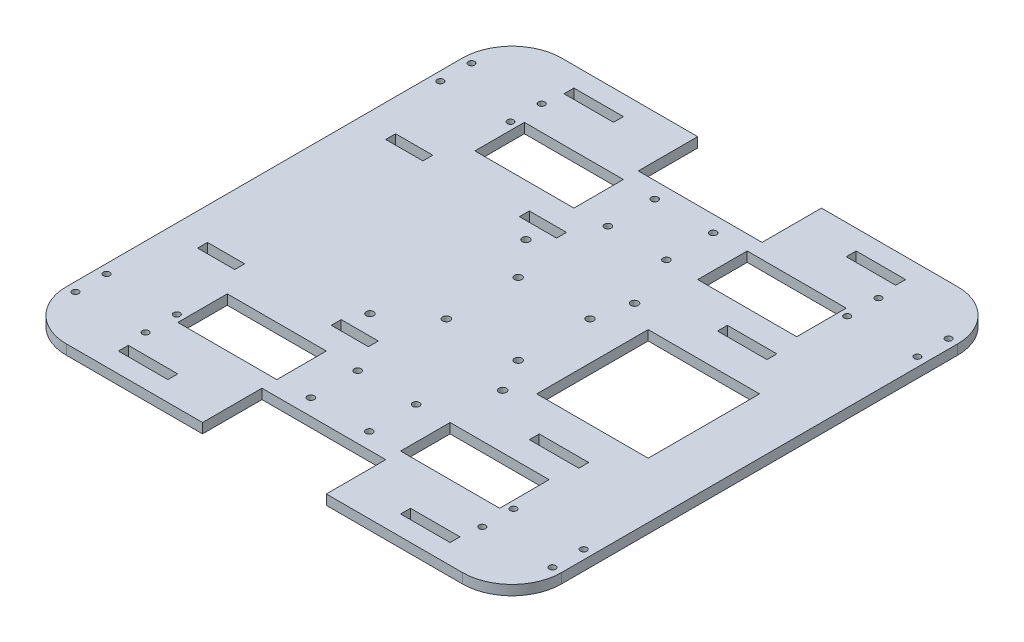
SolidWorks part; units mm, degrees
ref_plane "Front Plane" through (0, 0, 0) normal (0, 0, 1) x (1, 0, 0)
ref_plane "Top Plane" through (0, 0, 0) normal (0, 1, 0) x (1, 0, 0)
ref_plane "Right Plane" through (0, 0, 0) normal (1, 0, 0) x (0, 0, -1)
sketch "Sketch1" plane through (0, 0, 0) normal (0, 1, 0) x (1, 0, 0)
  line L1 (-127, -127) -> (127, -127)
  line L2 (-127, -127) -> (-127, 127)
  line L3 (-127, 127) -> (127, 127)
  line L4 (127, -127) -> (127, 127)
  line L5 (-127, -127) -> (127, 127) construction
  line L6 (-127, 127) -> (127, -127) construction
  point P0 (0, 0)
  dimension "D1" = 254
  dimension "D2" = 254
extrude "Platform-Base" add sketch "Sketch1" along normal blind 5.08
sketch "Sketch9" plane through (0, 5.08, 0) normal (0, 1, 0) x (1, 0, 0)
  line L0 (-127, 0) -> (-85.09, 0) construction
  line L1 (-127, 127) -> (-127, -127) construction
  line L2 (-85.09, 0) -> (-85.09, -116.84) construction
  line L3 (-85.09, 0) -> (-85.09, 116.84) construction
  line L4 (-85.09, 0) -> (85.09, 0) construction
  line L5 (85.09, 0) -> (127, 0) construction
  line L6 (127, -127) -> (127, 127) construction
  line L7 (85.09, 0) -> (85.09, 116.84) construction
  line L8 (85.09, 0) -> (85.09, -116.84) construction
  line L9 (-85.09, -116.84) -> (-127, -116.84) construction
  line L10 (-85.09, -116.84) -> (-85.09, -127) construction
  line L11 (-85.09, -116.84) -> (-59.69, -116.84)
  line L12 (-85.09, -116.84) -> (-85.09, -111.76)
  line L13 (-85.09, -111.76) -> (-59.69, -111.76)
  line L14 (-59.69, -116.84) -> (-59.69, -111.76)
  line L15 (85.09, -116.84) -> (59.69, -116.84)
  line L16 (85.09, -116.84) -> (85.09, -111.76)
  line L17 (85.09, -111.76) -> (59.69, -111.76)
  line L18 (59.69, -116.84) -> (59.69, -111.76)
  line L19 (85.09, 116.84) -> (59.69, 116.84)
  line L20 (85.09, 116.84) -> (85.09, 111.76)
  line L21 (85.09, 111.76) -> (59.69, 111.76)
  line L22 (59.69, 116.84) -> (59.69, 111.76)
  line L23 (-85.09, 116.84) -> (-59.69, 116.84)
  line L24 (-85.09, 116.84) -> (-85.09, 111.76)
  line L25 (-85.09, 111.76) -> (-59.69, 111.76)
  line L26 (-59.69, 116.84) -> (-59.69, 111.76)
  line L27 (-127, -127) -> (127, -127) construction
  line L28 (59.69, 50.8) -> (-22.86, 50.8) construction
  line L29 (59.69, -111.76) -> (59.69, -50.8) construction
  line L34 (59.69, 45.72) -> (59.69, 0) construction
  line L35 (-22.86, 50.8) -> (-41.91, 50.8) construction
  line L36 (-41.91, 50.8) -> (-91.44, 50.8) construction
  line L37 (59.69, -50.8) -> (85.09, -50.8)
  line L38 (59.69, -50.8) -> (59.69, -45.72)
  line L39 (59.69, -45.72) -> (85.09, -45.72)
  line L40 (85.09, -50.8) -> (85.09, -45.72)
  line L41 (59.69, 50.8) -> (85.09, 50.8)
  line L42 (59.69, 50.8) -> (59.69, 45.72)
  line L43 (59.69, 45.72) -> (85.09, 45.72)
  line L44 (85.09, 50.8) -> (85.09, 45.72)
  line L49 (-91.44, 50.8) -> (-110.49, 50.8) construction
  line L50 (-110.49, 50.8) -> (-127, 50.8) construction
  line L51 (-22.86, 45.72) -> (-22.86, -45.72) construction
  line L52 (-22.86, 50.8) -> (-41.91, 50.8)
  line L53 (-22.86, 50.8) -> (-22.86, 45.72)
  line L54 (-22.86, 45.72) -> (-41.91, 45.72)
  line L55 (-41.91, 50.8) -> (-41.91, 45.72)
  line L56 (-91.44, 50.8) -> (-110.49, 50.8)
  line L57 (-91.44, 50.8) -> (-91.44, 45.72)
  line L58 (-91.44, 45.72) -> (-110.49, 45.72)
  line L59 (-110.49, 50.8) -> (-110.49, 45.72)
  line L68 (-41.91, -45.72) -> (-91.4459, -45.72) construction
  line L69 (59.69, -50.8) -> (-22.86, -50.8) construction
  line L70 (-22.86, -45.72) -> (-41.91, -45.72)
  line L71 (59.69, -45.72) -> (59.69, 0) construction
  line L72 (-22.86, -45.72) -> (-22.86, -50.8)
  line L73 (-22.86, -50.8) -> (-41.91, -50.8)
  line L74 (-41.91, -45.72) -> (-41.91, -50.8)
  line L75 (-91.4459, -45.72) -> (-110.4959, -45.72)
  line L76 (-91.4459, -45.72) -> (-91.4459, -50.8)
  line L77 (-91.4459, -50.8) -> (-110.4959, -50.8)
  line L78 (-110.4959, -45.72) -> (-110.4959, -50.8)
  dimension "D1" = 41.91
  dimension "D2" = 5.08
  dimension "D3" = 25.4
  dimension "D4" = 10.16
  dimension "D6" = 16.51
  dimension "D7" = 19.05
  dimension "D8" = 49.53
  dimension "D9" = 19.05
  dimension "D5" = 45.72
extrude "Cut-Extrude6" cut sketch "Sketch9" against normal through all
ref_axis "Axis1" through (-127, 5.08, 0) along (0, -1, 0)
ref_plane "Plane1" through (0, 0, 0) normal (0, 0, 1) x (0, -1, 0)
sketch "Sketch3" plane through (0, 5.08, 0) normal (0, 1, 0) x (1, 0, 0)
  line L0 (127, 0) -> (-126.5787, 0) construction
  line L1 (127, -127) -> (127, 127) construction
  line L2 (-127, -127) -> (127, -127) construction
  line L3 (0, -127) -> (0, 127) construction
  line L4 (127, 127) -> (-127, 127) construction
  line L5 (0.2106, 0) -> (0, -76.2) construction
  line L7 (15, -64.2) -> (-15, -64.2) construction
  line L8 (15, -64.2) -> (15, -88.2) construction
  line L9 (15, -88.2) -> (-15, -88.2) construction
  line L10 (-15, -64.2) -> (-15, -88.2) construction
  line L11 (15, -64.2) -> (-15, -88.2) construction
  line L12 (15, -88.2) -> (-15, -64.2) construction
  circle A0 centre (15, -64.2) radius 1.75
  circle A1 centre (15, -88.2) radius 1.75
  circle A2 centre (-15, -88.2) radius 1.75
  circle A3 centre (-15, -64.2) radius 1.75
  dimension "D1" = 76.2
  dimension "D2" = 24
  dimension "D3" = 30
extrude "Cut-Extrude1" cut sketch "Sketch3" against normal through all
mirror "Mirror2" about plane through (0, 0, 0) normal (0, 0, 1) of "Cut-Extrude1"
sketch "Sketch4" plane through (0, 5.08, 0) normal (0, 1, 0) x (1, 0, 0)
  line L0 (-127, -127) -> (127, -127) construction
  line L1 (0, -127) -> (0, -111.76) construction
  line L3 (31.75, -96.52) -> (-31.75, -96.52)
  line L4 (31.75, -96.52) -> (31.75, -127)
  line L5 (31.75, -127) -> (-31.75, -127)
  line L6 (-31.75, -96.52) -> (-31.75, -127)
  line L7 (31.75, -96.52) -> (-31.75, -127) construction
  line L8 (31.75, -127) -> (-31.75, -96.52) construction
  dimension "D1" = 63.5
  dimension "D2" = 30.48
  dimension "D3" = 15.24
extrude "Cut-Extrude2" cut sketch "Sketch4" against normal through all
mirror "Mirror3" about plane through (0, 0, 0) normal (0, 0, 1) of "Cut-Extrude2"
ref_axis "Axis5" [suppressed] through (0, 7.62, -96.52) along (0, 0, 1)
ref_plane "Plane2" [suppressed] through (0, 0, 0) normal (-1, 0, 0) x (0, 0, 1)
fillet "Corner-Rounding" radius 25.4 4 edges at (-127, 2.54, -127) (127, 2.54, -127) (127, 2.54, 127) (-127, 2.54, 127)
sketch "Sketch8" plane through (0, 5.08, 0) normal (0, 1, 0) x (1, 0, 0)
  line L0 (-127, 0) -> (69.85, 0) construction
  line L1 (-127, 101.6) -> (-127, -101.6) construction
  line L4 (41.275, 28.575) -> (98.425, 28.575)
  line L5 (41.275, 28.575) -> (41.275, -28.575)
  line L6 (41.275, -28.575) -> (98.425, -28.575)
  line L7 (98.425, 28.575) -> (98.425, -28.575)
  line L8 (41.275, 28.575) -> (98.425, -28.575) construction
  line L9 (41.275, -28.575) -> (98.425, 28.575) construction
  dimension "D1" = 196.85
  dimension "D2" = 57.15
  dimension "D3" = 57.15
extrude "Cut-Extrude5" cut sketch "Sketch8" against normal through all
sketch "Sketch10" plane through (0, 5.08, 0) normal (0, 1, 0) x (1, 0, 0)
  line L0 (-127, -88.9) -> (-82.55, -88.9) construction
  line L1 (-127, 101.6) -> (-127, -101.6) construction
  line L2 (-82.55, -88.9) -> (-82.55, -127) construction
  line L3 (-101.6, -127) -> (-31.75, -127) construction
  line L5 (-82.55, -88.9) -> (-31.75, -88.9)
  line L6 (-82.55, -88.9) -> (-82.55, -63.5)
  line L7 (-82.55, -63.5) -> (-31.75, -63.5)
  line L8 (-31.75, -88.9) -> (-31.75, -63.5)
  dimension "D1" = 38.1
  dimension "D2" = 44.45
  dimension "D3" = 25.4
  dimension "D4" = 50.8
extrude "Cut-Extrude7" cut sketch "Sketch10" against normal through all
sketch "Sketch11" plane through (0, 5.08, 0) normal (0, 1, 0) x (1, 0, 0)
  line L0 (41.275, 0) -> (3.175, 0) construction
  line L1 (41.275, 28.575) -> (41.275, -28.575) construction
  line L3 (21.59, 18.415) -> (-15.24, 18.415) construction
  line L4 (21.59, 18.415) -> (21.59, -18.415) construction
  line L5 (21.59, -18.415) -> (-15.24, -18.415) construction
  line L6 (-15.24, 18.415) -> (-15.24, -18.415) construction
  line L7 (21.59, 18.415) -> (-15.24, -18.415) construction
  line L8 (21.59, -18.415) -> (-15.24, 18.415) construction
  circle A0 centre (-15.24, -18.415) radius 1.905
  circle A1 centre (-15.24, 18.415) radius 1.905
  circle A2 centre (21.59, 18.415) radius 1.905
  circle A3 centre (21.59, -18.415) radius 1.905
  dimension "D2" = 3.81
  dimension "D1" = 36.83
  dimension "D3" = 38.1
extrude "Cut-Extrude8" cut sketch "Sketch11" against normal through all
sketch "Sketch12" plane through (0, 5.08, 0) normal (0, 1, 0) x (1, 0, 0)
  line L0 (30.9279, -35.7049) -> (-37.1441, -35.7049) construction
  line L1 (-37.1441, -35.7049) -> (-30.0321, 37.1931) construction
  line L2 (-30.0321, 37.1931) -> (26.1019, 36.7786) construction
  line L3 (26.1019, 36.7786) -> (30.9279, -35.7049) construction
  line L4 (30.9279, -35.7049) -> (127, -35.7049) construction
  line L5 (127, -101.6) -> (127, 101.6) construction
  line L6 (30.9279, -35.7049) -> (30.9279, -96.52) construction
  line L7 (31.75, -96.52) -> (-31.75, -96.52) construction
  line L8 (30.9279, -35.7049) -> (30.9279, 36.7786) construction
  line L9 (30.9279, 36.7786) -> (26.1019, 36.7786) construction
  circle A0 centre (30.9279, -35.7049) radius 1.905
  circle A1 centre (-37.1441, -35.7049) radius 1.905
  circle A2 centre (26.1019, 36.7786) radius 1.905
  circle A3 centre (-30.0321, 37.1931) radius 1.905
  dimension "D1" = 3.81
  dimension "D2" = 68.072
  dimension "D3" = 72.898
  dimension "D4" = 56.134
  dimension "D5" = 72.644
  dimension "D6" = 4.826
extrude "Cut-Extrude9" cut sketch "Sketch12" against normal through all
sketch "Sketch13" plane through (0, 5.08, 0) normal (0, 1, 0) x (1, 0, 0)
  line L0 (-86.36, -127) -> (-86.36, -101.6) construction
  line L1 (-101.6, -127) -> (-31.75, -127) construction
  line L2 (-86.36, -101.6) -> (-127, -101.6) construction
  line L3 (-127, 101.6) -> (-127, -101.6) construction
  line L5 (-86.36, -101.6) -> (-122.36, -101.6) construction
  line L6 (-86.36, -101.6) -> (-86.36, -85.6) construction
  line L7 (-86.36, -85.6) -> (-122.36, -85.6) construction
  line L8 (-122.36, -101.6) -> (-122.36, -85.6) construction
  circle A0 centre (-86.36, -101.6) radius 1.651
  circle A1 centre (-122.36, -101.6) radius 1.651
  circle A2 centre (-122.36, -85.6) radius 1.651
  circle A3 centre (-86.36, -85.6) radius 1.651
  dimension "D5" = 3.302
  dimension "D1" = 25.4
  dimension "D2" = 40.64
  dimension "D3" = 16
  dimension "D4" = 36
extrude "Cut-Extrude10" cut sketch "Sketch13" against normal through all
mirror "Mirror4" about plane through (0, 0, 0) normal (0, 0, 1) of "Cut-Extrude10"
mirror "Mirror5" about plane through (0, 0, 0) normal (1, 0, 0) of "Mirror4"
mirror "Mirror6" about plane through (0, 0, 0) normal (1, 0, 0) of "Cut-Extrude7"
mirror "Mirror7" about plane through (0, 0, 0) normal (0, 0, 1) of "Mirror6"
equation "\"Foamcore\" = .1in"
equation "\"MDF\" = .2in"
equation "\"Gmaterial\"= \"MDF\""
equation "\"D1@Platform-Base\" = \"Gmaterial\""
equation "\"D2@Sketch9\"=\"Gmaterial\""
equation "\"D5@Sketch9\"=2-\"Gmaterial\""
